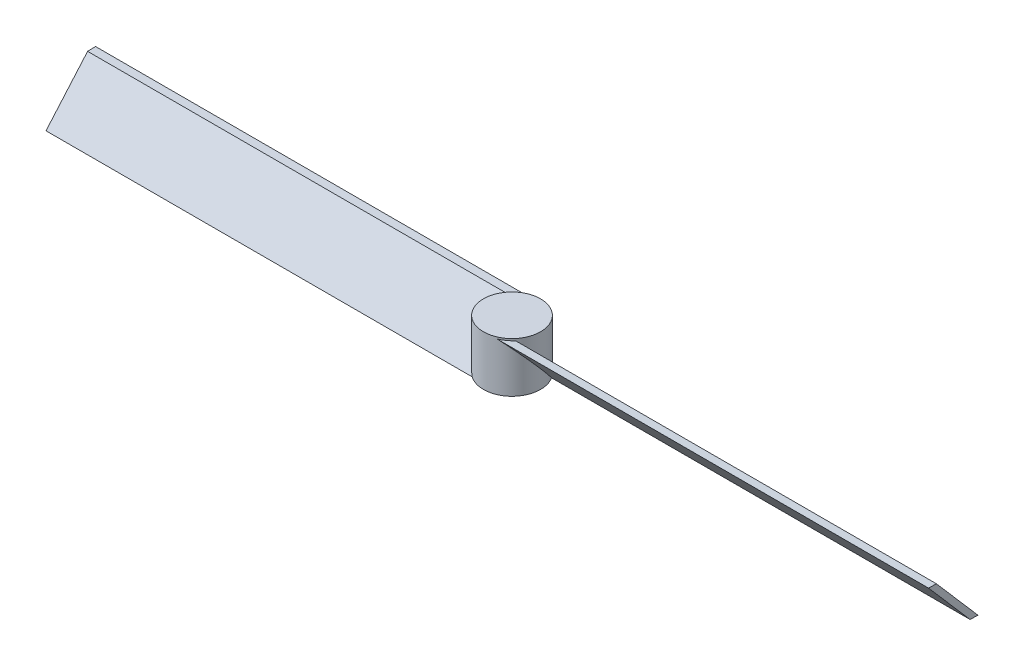
SolidWorks part; units mm, degrees
ref_plane "Front Plane" through (0, 0, 0) normal (0, 0, 1) x (1, 0, 0)
ref_plane "Top Plane" through (0, 0, 0) normal (0, 1, 0) x (1, 0, 0)
ref_plane "Right Plane" through (0, 0, 0) normal (1, 0, 0) x (0, 0, -1)
sketch "Sketch1" plane through (0, 0, 0) normal (0, 1, 0) x (1, 0, 0)
  circle A0 centre (0, 0) radius 2
extrude "Boss-Extrude1" add sketch "Sketch1" along normal blind 3.5
sketch "Sketch2" plane through (0, 0, 0) normal (0, 1, 0) x (1, 0, 0)
  circle A0 centre (0, 0) radius 0.42
extrude "Cut-Extrude1" cut sketch "Sketch2" along normal blind 2.5
sketch "Sketch3" plane through (0, 0, 0) normal (1, 0, 0) x (0, 0, -1)
  line L0 (1.6275, 0) -> (-1.2839, 3.3629)
  line L1 (1.6275, 0) -> (1.0729, 0.0168)
  line L2 (-1.2839, 3.3629) -> (-1.8386, 3.3798)
  line L3 (1.0729, 0.0168) -> (-1.8386, 3.3798)
extrude "Boss-Extrude2" add sketch "Sketch3" along normal blind 31
sketch "Sketch4" plane through (0, 0, 0) normal (-1, 0, 0) x (0, 0, 1)
  line L0 (1.6275, 0) -> (-1.2839, 3.3629)
  line L1 (1.6275, 0) -> (1.0729, 0.0168)
  line L2 (-1.2839, 3.3629) -> (-1.8386, 3.3798)
  line L3 (1.0729, 0.0168) -> (-1.8386, 3.3798)
extrude "Boss-Extrude3" add sketch "Sketch4" along normal blind 31
